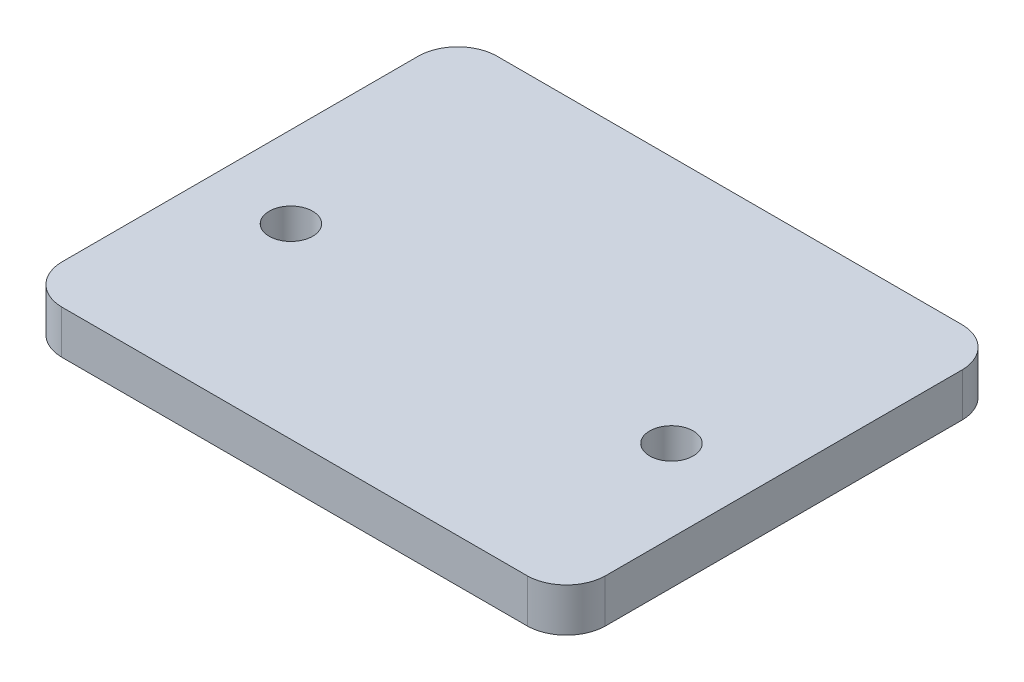
SolidWorks part; units mm, degrees
ref_plane "Front Plane" through (0, 0, 0) normal (0, 0, 1) x (1, 0, 0)
ref_plane "Top Plane" through (0, 0, 0) normal (0, 1, 0) x (1, 0, 0)
ref_plane "Right Plane" through (0, 0, 0) normal (1, 0, 0) x (0, 0, -1)
sketch "Sketch1" plane through (0, 0, 0) normal (0, 1, 0) x (1, 0, 0)
  line L0 (0, -3.7692) -> (0, -12.0494) construction
  line L5 (-25, 20) -> (25, 20)
  line L6 (-25, 20) -> (-25, -20)
  line L7 (-25, -20) -> (25, -20)
  line L8 (25, 20) -> (25, -20)
  line L9 (-25, 20) -> (25, -20) construction
  line L10 (-25, -20) -> (25, 20) construction
  line L11 (-5.3094, 0) -> (-10.9893, 0) construction
  circle A0 centre (0, 5.2766) radius 4.5
  circle A1 centre (-17.5072, -2.826) radius 2
  circle A2 centre (17.4928, -2.826) radius 2
  arc A3 (-25, -16.277) -> (-21.447, -20) centre (-21.362, -16.362) ccw
  arc A4 (-25, 16.277) -> (-21.447, 20) centre (-21.362, 16.362) cw
  arc A5 (25, 16.277) -> (21.447, 20) centre (21.362, 16.362) ccw
  arc A6 (25, -16.277) -> (21.447, -20) centre (21.362, -16.362) cw
  circle A7 centre (0, 5.2766) radius 3
  point P0 (0, 0)
  dimension "D3" = 9
  dimension "D1" = 50
  dimension "D2" = 40
extrude "Boss-Extrude2" add sketch "Sketch1" along normal blind 4 contours A6 L8 A5 L5 A4 L6 A3 L7 A2 A1 A0 | A0 A7 | A7 region at (0.0001, 0, 0.1393) region at (-4.3727, 0, -5.2766) region at (0, 0, -5.2766)
extrude "Cut-Extrude4" cut sketch "Sketch1<8>" along normal blind 2 contours A0 A7 | A7 region at (-4.3727, 0, -5.2766)
sketch "Sketch1<8>" plane through (0, 0, 0) normal (0, 1, 0) x (1, 0, 0) same geometry as "Sketch1"
